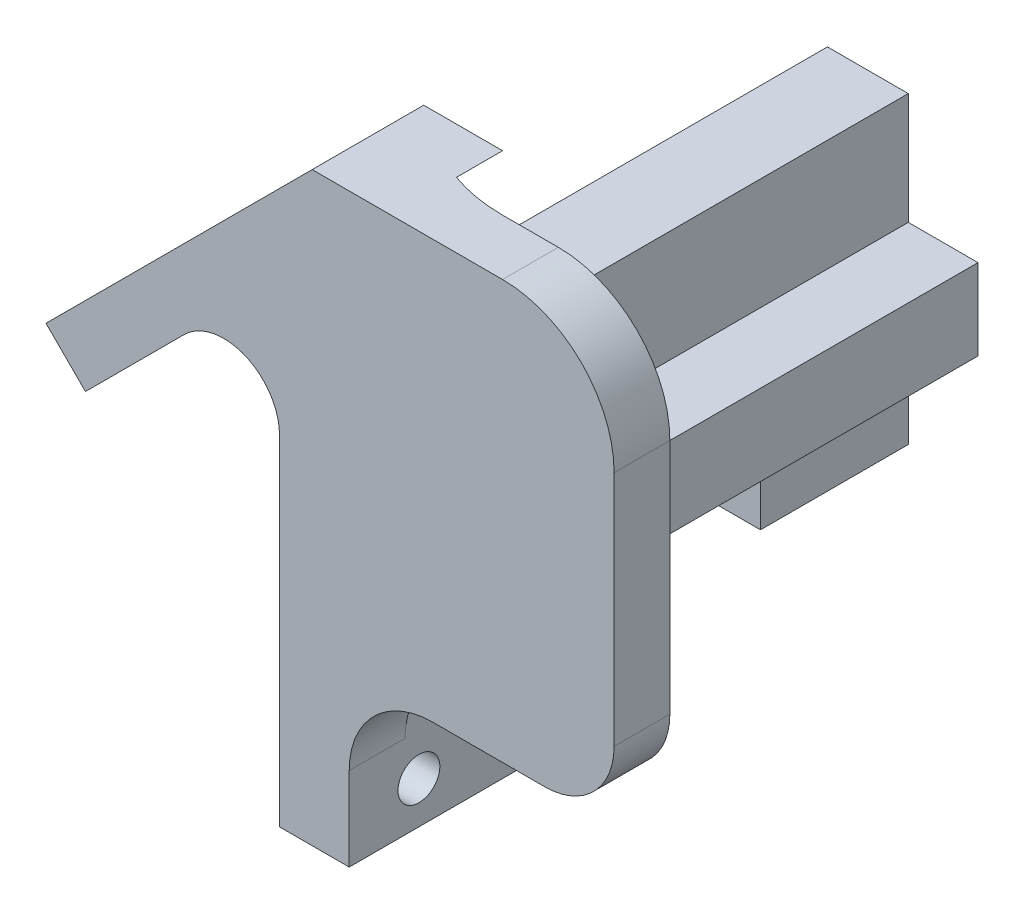
SolidWorks part; units mm, degrees
ref_plane "Front Plane" through (0, 0, 0) normal (0, 0, 1) x (1, 0, 0)
ref_plane "Top Plane" through (0, 0, 0) normal (0, 1, 0) x (1, 0, 0)
ref_plane "Right Plane" through (0, 0, 0) normal (1, 0, 0) x (0, 0, -1)
sketch "Sketch1" plane through (0, 0, 0) normal (0, 0, 1) x (1, 0, 0)
  line L0 (0, 0) -> (0, 8)
  line L1 (0, 8) -> (6, 8)
  line L2 (6, 8) -> (6, 0)
  line L3 (6, 0) -> (11, 0)
  line L4 (11, 0) -> (11, -6)
  line L5 (11, -6) -> (6, -6)
  line L6 (6, -6) -> (6, -14)
  line L7 (6, -14) -> (0, -14)
  line L8 (0, -14) -> (0, -6)
  line L9 (0, 0) -> (-5, 0)
  line L10 (-5, 0) -> (-5, -6)
  line L11 (-5, -6) -> (0, -6)
  dimension "D1" = 6
  dimension "D2" = 5
  dimension "D3" = 8
extrude "Boss-Extrude1" add sketch "Sketch1" along normal blind 28.2
sketch "Sketch2" plane through (6, 0, 0) normal (1, 0, 0) x (0, 0, -1)
  line L0 (-14.1, -6) -> (-14.1, -14) construction
  line L1 (-28.2, -6) -> (0, -6) construction
  line L2 (-28.2, -14) -> (0, -14) construction
  line L3 (-17.6, -14) -> (-17.6, -9)
  line L4 (-17.6, -9) -> (-10.6, -9)
  line L5 (-10.6, -9) -> (-10.6, -14)
  line L6 (-10.6, -14) -> (-17.6, -14)
  point P8 (-14.1, -9)
  dimension "D1" = 5
  dimension "D2" = 7
extrude "Cut-Extrude1" cut sketch "Sketch2" against normal through all
sketch "Sketch3" plane through (0, 0, 28.2) normal (0, 0, 1) x (1, 0, 0)
  line L0 (0, 10) -> (7, 10) construction
  line L1 (13, 4) -> (13, -13) construction
  line L2 (10, -16) -> (-7, -16) construction
  line L3 (-7, -16) -> (-7, 4) construction
  line L4 (-1, 10) -> (0, 10) construction
  line L5 (0, 0) -> (0, 10) construction
  line L6 (0, 12) -> (7, 12)
  line L7 (15, 4) -> (15, -13)
  line L8 (10, -18) -> (-9, -18)
  line L9 (-9, -18) -> (-9, 4)
  line L10 (-1, 12) -> (0, 12)
  arc A0 (13, 4) -> (7, 10) centre (7, 4) ccw construction
  arc A1 (-7, 4) -> (-1, 10) centre (-1, 4) cw construction
  arc A2 (10, -16) -> (13, -13) centre (10, -13) ccw construction
  arc A3 (15, 4) -> (7, 12) centre (7, 4) ccw
  arc A4 (10, -18) -> (15, -13) centre (10, -13) ccw
  arc A5 (-9, 4) -> (-1, 12) centre (-1, 4) cw
  point P9 (13, 10)
  point P12 (-7, 10)
  point P15 (13, -16)
  dimension "D5" = 6
  dimension "D6" = 3
  dimension "D1" = 10
  dimension "D2" = 26
  dimension "D3" = 20
  dimension "D4" = 7
  dimension "D7" = 2
extrude "Boss-Extrude2" add sketch "Sketch3" along normal blind 2
sketch "Sketch4" plane through (0, 0, 30.2) normal (0, 0, 1) x (1, 0, 0)
  line L0 (-9, -18) -> (-9, 4)
  line L1 (-9, -18) -> (10, -18)
  line L2 (15, -13) -> (15, 4)
  line L3 (7, 12) -> (-1, 12)
  line L4 (15, -13) -> (15, 4) construction
  line L5 (7, 12) -> (-1, 12) construction
  line L6 (13.8, -13) -> (13.8, 4)
  line L7 (7, 10.8) -> (-1, 10.8)
  line L8 (-7.8, -16.8) -> (-7.8, 4)
  line L9 (-7.8, -16.8) -> (10, -16.8)
  arc A1 (7, 12) -> (15, 4) centre (7, 4) cw
  arc A2 (-9, 4) -> (-1, 12) centre (-1, 4) cw
  arc A3 (10, -18) -> (15, -13) centre (10, -13) ccw
  arc A4 (7, 10.8) -> (13.8, 4) centre (7, 4) cw
  arc A5 (-7.8, 4) -> (-1, 10.8) centre (-1, 4) cw
  arc A6 (10, -16.8) -> (13.8, -13) centre (10, -13) ccw
  dimension "D1" = 8
  dimension "D2" = 5
  dimension "D3" = 1.2
extrude "Boss-Extrude3" add sketch "Sketch4" against normal blind 4
sketch "Sketch5" plane through (0, -18, 0) normal (0, -1, 0) x (1, 0, 0)
  line L0 (-9, 30.2) -> (-4, 30.2)
  line L1 (-9, 30.2) -> (10, 30.2) construction
  line L2 (-4, 30.2) -> (-4, 15.2)
  line L3 (-4, 15.2) -> (-9, 15.2)
  line L4 (-9, 15.2) -> (-9, 30.2)
  dimension "D1" = 5
  dimension "D2" = 15
extrude "Boss-Extrude4" add sketch "Sketch5" along normal blind 12
fillet "Fillet1" radius 6 1 edges at (-4, -18, 28.2)
fillet "Fillet2" radius 10 1 edges at (-6.5, -18, 26.2)
sketch "Sketch6" plane through (-9, 0, 0) normal (-1, 0, 0) x (0, 0, 1)
  line L0 (19.2, -21) -> (25.2, -21) construction
  line L1 (25.2, -21) -> (25.2, -27) construction
  line L2 (25.2, -27) -> (19.2, -21) construction
  line L3 (15.2, -30) -> (15.2, -18) construction
  line L5 (16.2, -18) -> (15.2, -18) construction
  circle A0 centre (19.2, -21) radius 1.5
  circle A1 centre (25.2, -27) radius 1.5
  point P9 (15.7, -18)
  dimension "D1" = 3
  dimension "D5" = 3
  dimension "D2" = 6
  dimension "D3" = 4
  dimension "D4" = 6
extrude "Cut-Extrude2" cut sketch "Sketch6" against normal through all
sketch "Sketch7" plane through (0, 0, 30.2) normal (0, 0, 1) x (1, 0, 0)
  line L0 (-9, 4) -> (-22.9203, -9.9203)
  line L1 (-22.9203, -9.9203) -> (-25.7487, -7.0919)
  line L2 (-25.7487, -7.0919) -> (-6.6569, 12)
  line L3 (-6.6569, 12) -> (-1, 12)
  line L4 (-9, 4) -> (-9, -30) construction
  line L5 (-9, 4) -> (-6.6569, 9.6569)
  line L6 (-6.6569, 9.6569) -> (-1, 12)
  arc A0 (-1, 12) -> (-9, 4) centre (-1, 4) ccw construction
  point P9 (-24.3345, -8.5061)
  dimension "D1" = 45
  dimension "D2" = 2
  dimension "D3" = 27
extrude "Boss-Extrude5" add sketch "Sketch7" against normal blind 8
fillet "Fillet3" radius 10 1 edges at (-7.8284, 6.8284, 26.2)
sketch "Sketch9" plane through (-9.3284, 9.3284, 0) normal (-0.7071, 0.7071, 0) x (0, 0, 1)
  line L0 (22.2, -23.2218) -> (30.2, -23.2218) construction
  line L1 (26.2, -18.2218) -> (26.2, -23.2218) construction
  circle A0 centre (26.2, -18.2218) radius 1.5
  dimension "D1" = 3
  dimension "D2" = 5
extrude "Cut-Extrude3" cut sketch "Sketch9" against normal blind 8
fillet "Fillet4" radius 4 1 edges at (-9, 4, 26.2)
fillet "Fillet5" radius 1.2 2 edges at (3, -9, 17.6) (3, -9, 10.6)
sketch "Sketch10" plane through (0, 0, 0) normal (0, 0, -1) x (-1, 0, 0)
  line L0 (0, -14) -> (0, -6)
  line L1 (0, -6) -> (5, -6)
  line L2 (5, -6) -> (5, 0)
  line L3 (5, 0) -> (0, 0)
  line L4 (0, 0) -> (0, 8)
  line L5 (0, 8) -> (-6, 8)
  line L6 (-6, 8) -> (-6, 0)
  line L7 (-6, 0) -> (-11, 0)
  line L8 (-11, 0) -> (-11, -6)
  line L9 (-11, -6) -> (-6, -6)
  line L10 (-6, -6) -> (-6, -14)
  line L11 (-6, -14) -> (0, -14)
  line L12 (-0.1, -13.9) -> (-0.1, -5.9)
  line L13 (-0.1, -5.9) -> (4.9, -5.9)
  line L14 (4.9, -5.9) -> (4.9, -0.1)
  line L15 (4.9, -0.1) -> (-0.1, -0.1)
  line L16 (-0.1, -0.1) -> (-0.1, 7.9)
  line L17 (-0.1, 7.9) -> (-5.9, 7.9)
  line L18 (-5.9, 7.9) -> (-5.9, -0.1)
  line L19 (-5.9, -0.1) -> (-10.9, -0.1)
  line L20 (-10.9, -0.1) -> (-10.9, -5.9)
  line L21 (-10.9, -5.9) -> (-5.9, -5.9)
  line L22 (-5.9, -5.9) -> (-5.9, -13.9)
  line L23 (-5.9, -13.9) -> (-0.1, -13.9)
  dimension "D1" = 0.1
extrude "Cut-Extrude4" cut sketch "Sketch10" against normal blind 28.2
